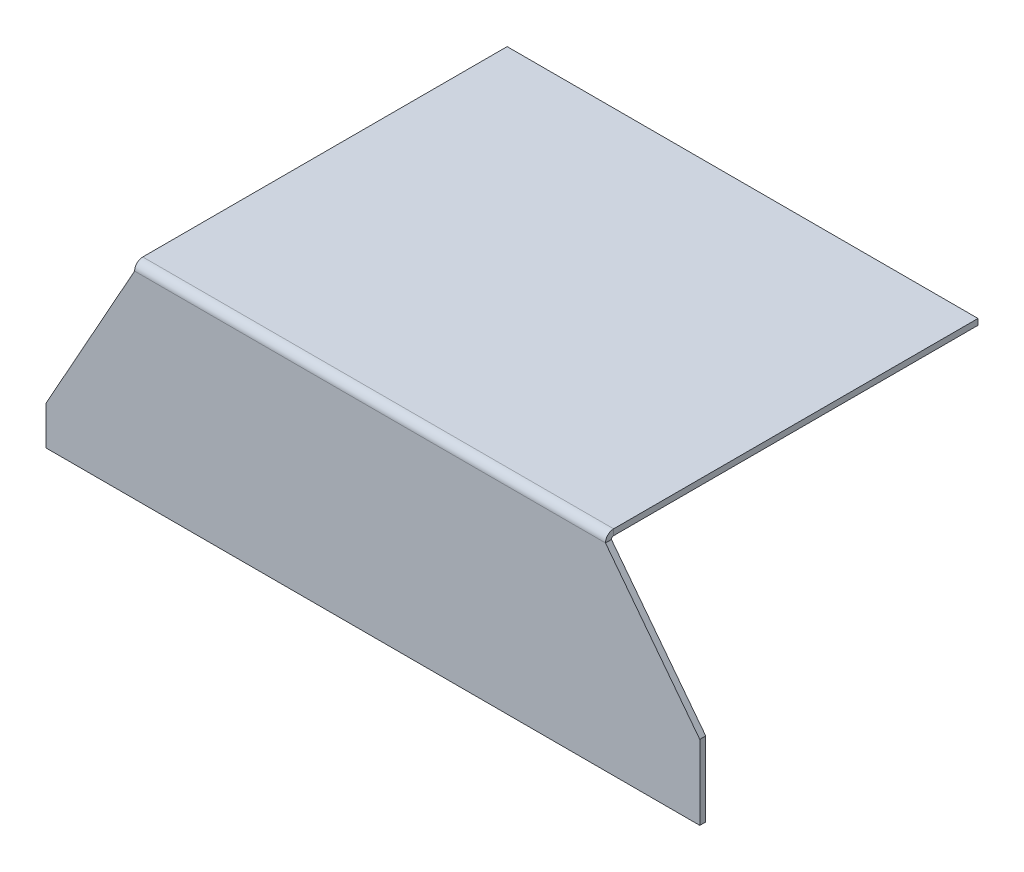
SolidWorks part; units mm, degrees
note: The reader was unsure of these and kept them because the rebuilt part matched: flange length of "边线-法兰1".
ref_plane "前视基准面" through (0, 0, 0) normal (0, 0, 1) x (1, 0, 0)
ref_plane "上视基准面" through (0, 0, 0) normal (0, 1, 0) x (1, 0, 0)
ref_plane "右视基准面" through (0, 0, 0) normal (1, 0, 0) x (0, 0, -1)
sketch "草图1" plane through (0, 0, 0) normal (0, 1, 0) x (1, 0, 0)
  line L1 (-79, -62.5) -> (79, -62.5)
  line L2 (-79, -62.5) -> (-79, 62.5)
  line L3 (-79, 62.5) -> (79, 62.5)
  line L4 (79, -62.5) -> (79, 62.5)
  line L5 (-79, -62.5) -> (79, 62.5) construction
  line L6 (-79, 62.5) -> (79, -62.5) construction
  point P0 (0, 0)
  dimension "D1" = 158
  dimension "D2" = 125
base flange "基体-法兰1" sketch "草图1" thickness 2 reverse thickness direction no parameters "D1"=0.7366
edge flange "边线-法兰1" sketch "草图8" flange angle 90 flange length 69 flange position material inside bend radius 0.7366 thickness 2 relief rectangular parameters "D6"=10
sketch "草图8" plane through (0, -2, 62.5) normal (0, 0, -1) x (1, 0, 0)
  line L2 (-79, 0) -> (-79, 67)
  line L3 (-79, 67) -> (79, 67)
  line L4 (79, 67) -> (79, 0)
  line L5 (79, 0) -> (-79, 0) construction
  line L6 (79, 0) -> (-79, 0)
bend "边线折弯1" bend radius 0.7366 bend angle 90 parameters "D5"=1
sketch "草图9" plane through (0, 0, 62.5) normal (0, 0, 1) x (1, 0, 0)
  line L0 (-79, -2.7366) -> (-108.7323, -56)
  line L1 (-108.7323, -56) -> (-108.7323, -69)
  line L2 (-108.7323, -69) -> (110.6438, -69)
  line L3 (110.6438, -69) -> (110.6438, -44)
  line L4 (110.6438, -44) -> (79, -2.7366)
  line L5 (79, -2.7366) -> (-79, -2.7366)
  line L6 (79, -69) -> (-79, -69) construction
  dimension "D1" = 52
  dimension "D2" = 25
  dimension "D3" = 13
  dimension "D4" = 61
base flange "薄片1" sketch "草图9" thickness 2 reverse thickness direction no parameters "D1"=0.7366
sketch "草图12" plane through (0, 0, 62.5) normal (0, 0, 1) x (1, 0, 0)
  line L6 (-10.7323, -61) -> (-10.7323, -10.7366)
  line L7 (-108.7323, -56) -> (-108.7323, -69) construction
  line L12 (-100.7323, -61) -> (102.6438, -61)
  line L13 (102.6438, -61) -> (102.6438, -46.7144)
  line L14 (102.6438, -46.7144) -> (75.0534, -10.7366)
  line L15 (75.0534, -10.7366) -> (-74.3037, -10.7366)
  line L16 (-74.3037, -10.7366) -> (-100.7323, -58.0817)
  line L17 (-100.7323, -58.0817) -> (-100.7323, -61)
  line L18 (-100.7323, -61) -> (102.6438, -61)
  line L19 (102.6438, -61) -> (102.6438, -46.7144)
  line L20 (102.6438, -46.7144) -> (75.0534, -10.7366)
  line L21 (75.0534, -10.7366) -> (-74.3037, -10.7366)
  line L22 (-74.3037, -10.7366) -> (-100.7323, -58.0817)
  line L23 (-100.7323, -58.0817) -> (-100.7323, -61)
  dimension "D2" = 98
  dimension "D1" = 8
sketch "折弯-线1" plane through (0, 0, 0) normal (0, 1, 0) x (1, 0, 0)
sketch "边界框1" plane through (0, 0, 0) normal (0, 1, 0) x (1, 0, 0)
sheet metal parameters "钣金7" thickness 2 parameters "D1"=0.7366
flat pattern "平板型式7" [suppressed]
sketch "折弯-线2" plane through (0, 0, 0) normal (0, 1, 0) x (1, 0, 0)
sketch "边界框2" [suppressed] plane through (0, 0, 0) normal (0, 1, 0) x (1, 0, 0)
sheet metal parameters "钣金8" thickness 2 parameters "D1"=0.7366
flat pattern "平板型式7" [suppressed]
sketch "折弯-线2" plane through (0, 0, 0) normal (0, 1, 0) x (1, 0, 0)
sketch "边界框2" [suppressed] plane through (0, 0, 0) normal (0, 1, 0) x (1, 0, 0)
bend of the flat pattern "展平-<边线折弯1>1"
sheet metal parameters "钣金9" thickness 2 parameters "D1"=0.7366
flat pattern "平板型式9" [suppressed]
sketch "折弯-线3" plane through (0, 0, 0) normal (0, 1, 0) x (1, 0, 0)
sketch "边界框3" [suppressed] plane through (0, 0, 0) normal (0, 1, 0) x (1, 0, 0)
bend of the flat pattern "展平-<边线折弯1>2"
